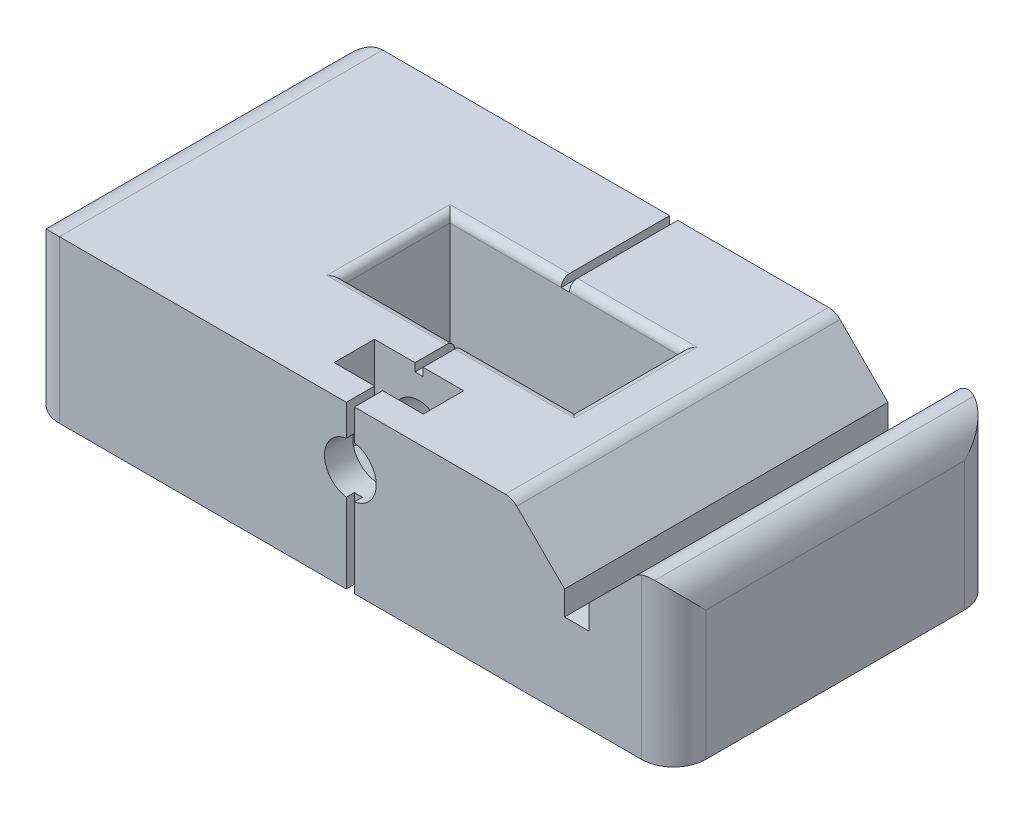
SolidWorks part; units mm, degrees
ref_plane "Front" through (0, 0, 0) normal (0, 0, 1) x (1, 0, 0)
ref_plane "Top" through (0, 0, 0) normal (0, 1, 0) x (1, 0, 0)
ref_plane "Right" through (0, 0, 0) normal (1, 0, 0) x (0, 0, -1)
sketch "Sketch1" plane through (0, 0, 0) normal (0, 1, 0) x (1, 0, 0)
  line L1 (-20, 10) -> (20, 10)
  line L2 (-20, 10) -> (-20, -10)
  line L3 (-20, -10) -> (20, -10)
  line L4 (20, 10) -> (20, -10)
  line L5 (0, -10) -> (0, 10) construction
  line L6 (-20, 0) -> (20, 0) construction
  point P4 (0, 0)
  point P140 (0, 0)
  dimension "D1" = 40
  dimension "D2" = 20
extrude "Boss-Extrude1" add sketch "Sketch1" along normal blind 10
sketch "Sketch2" plane through (0, 0, 0) normal (0, -1, 0) x (1, 0, 0)
  circle A0 centre (0, 0) radius 5.15
  circle A1 centre (12, 0) radius 5.15
  circle A2 centre (-12, 0) radius 5.15
  point P7 (0, 0)
  point P8 (0, 0)
  point P9 (0, 0)
  dimension "D1" = 10.3
  dimension "D2" = 12
  dimension "D3" = 12
extrude "Cut-Extrude1" cut sketch "Sketch2" against normal blind 2.4
sketch "Sketch3" plane through (0, 0, 10) normal (0, 0, 1) x (1, 0, 0)
  line L0 (18, 10) -> (14.75, 6.75)
  line L1 (-20, 10) -> (20, 10) construction
  line L2 (13.25, 6.75) -> (10, 10)
  line L3 (10, 10) -> (18, 10)
  line L4 (20, 10) -> (20, 0) construction
  line L5 (13.25, 6.75) -> (13.25, 5.25)
  line L6 (13.25, 5.25) -> (14.75, 5.25)
  line L7 (14.75, 5.25) -> (14.75, 6.75)
  point P1 (0, 0)
  point P9 (14, 5.25)
  dimension "D1" = 90
  dimension "D2" = 45
  dimension "D3" = 2
  dimension "D4" = 3.25
  dimension "D5" = 1.5
  dimension "D6" = 1.5
extrude "Cut-Extrude2" cut sketch "Sketch3" against normal through all
fillet "Fillet1" radius 2 6 edges at (20, 5, -10) (20, 10, 0) (20, 5, 10) (-20, 10, 0) (-20, 5, -10) (-20, 5, 10)
sketch "Sketch4" plane through (0, 0, 10) normal (0, 0, 1) x (1, 0, 0)
  line L0 (-18, 0) -> (18, 0) construction
  line L1 (-18, 10) -> (10, 10) construction
  line L3 (-0.25, 10) -> (0.25, 10)
  line L4 (-0.25, 10) -> (-0.25, 0)
  line L5 (-0.25, 0) -> (0.25, 0)
  line L6 (0.25, 10) -> (0.25, 0)
  line L7 (0, 0) -> (0, 10) construction
  line L8 (-0.25, 5) -> (0.25, 5) construction
  point P302 (0, 5)
  dimension "D1" = 0.5
extrude "Cut-Extrude3" cut sketch "Sketch4" against normal blind 0.5
sketch "Sketch5" plane through (0, 10, 0) normal (0, 1, 0) x (1, 0, 0)
  line L0 (0.25, -10) -> (10, -10) construction
  line L1 (10, 10) -> (-18, 10) construction
  line L2 (0.25, -9.5) -> (0.25, -10) construction
  line L3 (-0.25, -9.5) -> (-0.25, -10) construction
  line L5 (-0.25, 10) -> (0.25, 10)
  line L6 (-0.25, 10) -> (-0.25, -10)
  line L7 (-0.25, -10) -> (0.25, -10)
  line L8 (0.25, 10) -> (0.25, -10)
  line L9 (0, -10) -> (0, 10) construction
  line L10 (-0.25, 0) -> (0.25, 0) construction
  point P232 (0, 0)
extrude "Cut-Extrude4" cut sketch "Sketch5" against normal blind 0.5
sketch "Sketch6" plane through (0, 0, -10) normal (0, 0, -1) x (-1, 0, 0)
  line L0 (-10, 10) -> (-0.25, 10) construction
  line L1 (-0.25, 10) -> (0.25, 10)
  line L2 (-0.25, 10) -> (-0.25, 0)
  line L3 (-0.25, 0) -> (0.25, 0)
  line L4 (0.25, 10) -> (0.25, 0)
  line L5 (0, 0) -> (0, 10) construction
  line L6 (-0.25, 5) -> (0.25, 5) construction
  line L7 (-18, 0) -> (18, 0) construction
  line L8 (-0.25, 9.5) -> (-0.25, 10) construction
  line L9 (0.25, 9.5) -> (0.25, 10) construction
  point P320 (0, 5)
extrude "Cut-Extrude5" cut sketch "Sketch6" against normal blind 0.5
fillet "Fillet2" radius 1 2 edges at (10, 10, 0) (18, 10, 0)
ref_plane "Plane1" through (0, 50, 0) normal (0, 1, 0) x (1, 0, 0)
ref_axis "Optical Axis" through (0, 50, 50) along (0, 0, -1)
sketch "Sketch8" plane through (0, 0, 0) normal (0, 0, 1) x (1, 0, 0)
  line L11 (-18, 10) -> (-0.25, 10) construction
  line L12 (-7.15, 10) -> (7.15, 10)
  line L13 (-7.15, 10) -> (-7.15, 3)
  line L14 (-7.15, 3) -> (7.15, 3)
  line L15 (7.15, 10) -> (7.15, 3)
  line L16 (0, 3) -> (0, 10) construction
  line L17 (-7.15, 6.5) -> (7.15, 6.5) construction
  point P6 (0, 0)
  point P825 (0, 6.5)
  dimension "D1" = 14.3
  dimension "D2" = 7
extrude "Cut-Extrude7" cut sketch "Sketch8" against normal mid plane 6.6
sketch "Sketch9" plane through (0, 0, 10) normal (0, 0, 1) x (1, 0, 0)
  line L0 (0.25, 10) -> (9.5858, 10) construction
  circle A0 centre (0, 6.5) radius 1.6
  point P4 (0, 0)
  dimension "D1" = 3.2
  dimension "D2" = 3.5
extrude "Cut-Extrude8" cut sketch "Sketch9" against normal blind 10
ref_plane "Plane2" through (0, 0, 7) normal (0, 0, 1) x (1, 0, 0)
sketch "Sketch10" plane through (0, 0, 7) normal (0, 0, 1) x (1, 0, 0)
  line L0 (-2.76, 8.0935) -> (-2.76, 10)
  line L1 (0, 3.313) -> (2.76, 4.9065)
  line L2 (2.76, 4.9065) -> (2.76, 8.0819)
  line L5 (-2.76, 8.0935) -> (-2.76, 4.9065)
  line L6 (-2.76, 4.9065) -> (0, 3.313)
  line L7 (-18, 10) -> (-0.25, 10) construction
  line L8 (-2.76, 10) -> (2.76, 10)
  line L9 (0.25, 10) -> (9.5858, 10) construction
  line L10 (2.76, 10) -> (2.76, 8.0819)
  line L11 (-0.0201, 9.6754) -> (-1.3951, 8.8815) [skipped]
  line L12 (2.7399, 8.1051) -> (1.3649, 8.899) [skipped]
  circle A0 centre (0, 6.5) radius 2.76 construction
  arc A1 (-0.25, 8.0803) -> (-0.25, 4.9197) centre (0, 6.5) ccw construction
  point P22 (0, 0)
  dimension "D1" = 5.52
extrude "Cut-Extrude9" cut sketch "Sketch10" against normal mid plane 2.5
fillet "Fillet4" radius 0.5 6 edges at (3.7, 10, -3.3) (7.15, 10, 0) (3.7, 10, 3.3) (-3.7, 10, 3.3) (-7.15, 10, 0) (-3.7, 10, -3.3)
